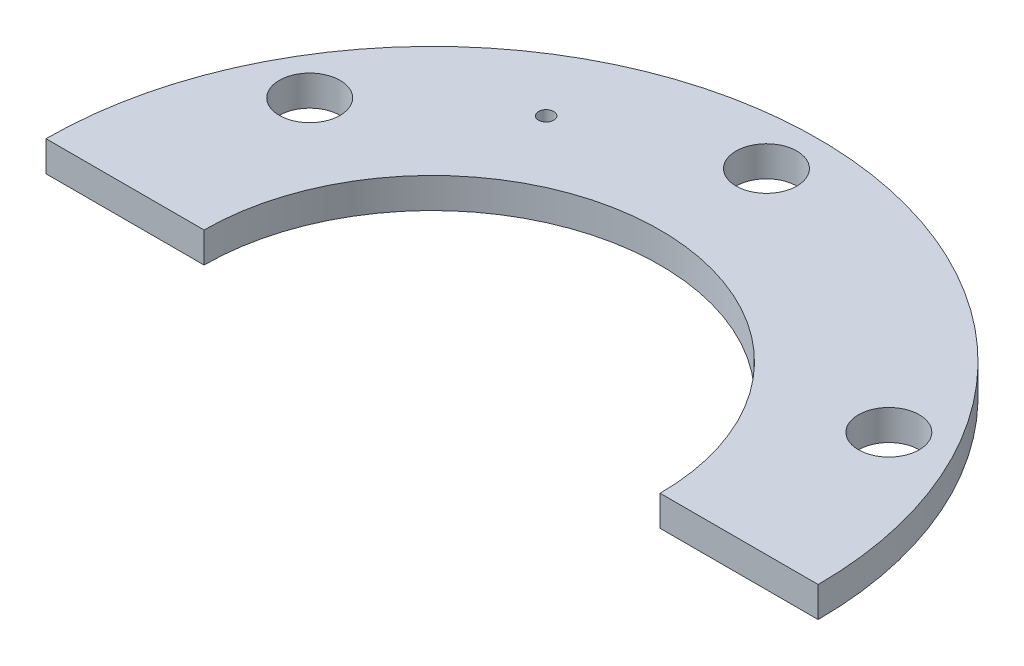
SolidWorks part; units mm, degrees
material "ABS"
ref_plane "Front Plane" through (0, 0, 0) normal (0, 0, 1) x (1, 0, 0)
ref_plane "Top Plane" through (0, 0, 0) normal (0, 1, 0) x (1, 0, 0)
ref_plane "Right Plane" through (0, 0, 0) normal (1, 0, 0) x (0, 0, -1)
sketch "Sketch1" plane through (0, 0, 0) normal (0, 1, 0) x (1, 0, 0)
  circle A0 centre (0, 0) radius 12.7
  dimension "D1" = 25.4
extrude "Boss-Extrude1" add sketch "Sketch1" along normal blind 1
sketch "Sketch19" plane through (0, 1, 0) normal (0, 1, 0) x (1, 0, 0)
  circle A0 centre (0, 11) radius 1
  circle A1 centre (9.5263, 5.5) radius 1
  circle A2 centre (9.5263, -5.5) radius 1
  circle A3 centre (0, -11) radius 1
  circle A4 centre (-9.5263, -5.5) radius 1
  circle A5 centre (-9.5263, 5.5) radius 1
  point P13 (0, 0)
  dimension "D1" = 2
  dimension "D2" = 11
  dimension "D3" = 6
extrude "Cut-Extrude1" cut sketch "Sketch19" against normal through all both and the other way through all
sketch "Sketch20" plane through (0, 1, 0) normal (0, 1, 0) x (1, 0, 0)
  circle A0 centre (0, 0) radius 7.5
  dimension "D1" = 15
extrude "Cut-Extrude2" cut sketch "Sketch20" against normal through all both and the other way through all
sketch "Sketch21" plane through (0, 0, 0) normal (0, 0, 1) x (1, 0, 0)
  line L1 (-36.7533, 32.3113) -> (29.1209, 32.3113)
  line L2 (-36.7533, 32.3113) -> (-36.7533, -19.668)
  line L3 (-36.7533, -19.668) -> (29.1209, -19.668)
  line L4 (29.1209, 32.3113) -> (29.1209, -19.668)
extrude "Cut-Extrude3" cut sketch "Sketch21" along normal through all
sketch "Sketch22" plane through (0, 1, 0) normal (0, 1, 0) x (1, 0, 0)
  line L0 (-9.5263, 5.5) -> (0, 11)
  line L1 (-5.125, 8.8768) -> (0, 0) construction
  circle A0 centre (-5.125, 8.8768) radius 0.25
  point P7 (-4.7631, 8.25)
  dimension "D1" = 0.5
  dimension "D2" = 10.25
  dimension "D3" = 0
extrude "Cut-Extrude4" cut sketch "Sketch22" against normal through all both and the other way through all contours L0 A0 | L0 L1 A0 | L1 L0 A0 region at (-5.125, 1, -8.8768)
